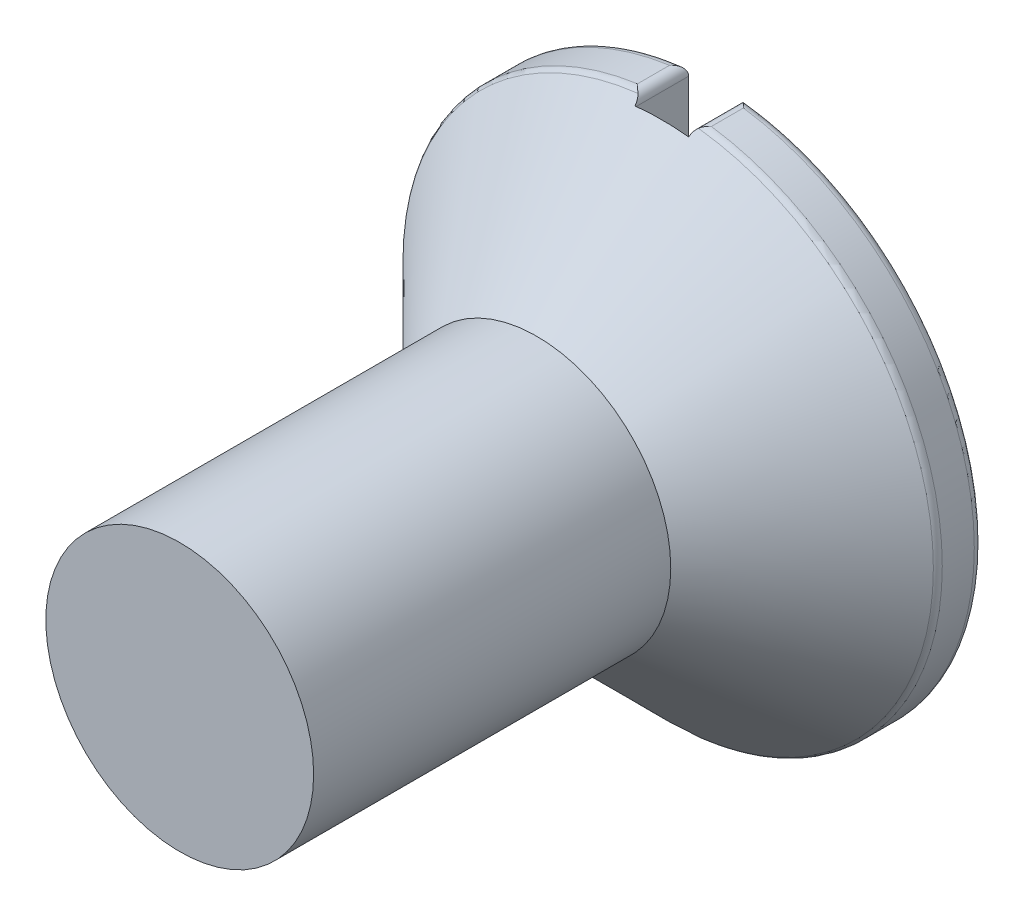
SolidWorks part; units mm, degrees
ref_plane "Front" through (0, 0, 0) normal (0, 0, 1) x (1, 0, 0)
ref_plane "Top" through (0, 0, 0) normal (0, 1, 0) x (1, 0, 0)
ref_plane "Right" through (0, 0, 0) normal (1, 0, 0) x (0, 0, -1)
sketch "Sketch1" plane through (0, 0, 0) normal (0, 0, 1) x (1, 0, 0)
  circle A0 centre (0, 0) radius 3
  dimension "D1" = 6
extrude "Base-Extrude" add sketch "Sketch1" along normal blind 1.5 draft 45
sketch "Sketch2" plane through (0, 0, 1.5) normal (0, 0, 1) x (1, 0, 0)
  circle A0 centre (0, 0) radius 1.5
  dimension "D1" = 3
extrude "Boss-Extrude1" add sketch "Sketch2" along normal blind 4
sketch "Sketch5" plane through (0, 0, 0) normal (0, 0, -1) x (-1, 0, 0)
  circle A0 centre (0, 0) radius 3
extrude "Boss-Extrude2" add sketch "Sketch5" along normal blind 0.5
sketch "Sketch6" plane through (0, 0, -0.5) normal (0, 0, -1) x (-1, 0, 0)
  line L1 (-0.3, 2.985) -> (0.3, 2.985)
  line L2 (-0.3, 2.985) -> (-0.3, -2.985)
  line L3 (-0.3, -2.985) -> (0.3, -2.985)
  line L4 (0.3, 2.985) -> (0.3, -2.985)
  circle A0 centre (0, 0) radius 3 construction
  dimension "D1" = 0.3
  dimension "D2" = 0.6
extrude "Cut-Extrude2" cut sketch "Sketch6" against normal blind 0.6
fillet "Fillet1" radius 0.1 12 edges at (3, 0, 0) (0.3, -2.985, -0.25) (-3, 0, 0) (-0.3, 2.985, -0.25) (3, 0, -0.5) (-3, 0, -0.5) (0.3, 2.985, -0.25) (-0.3, -2.985, -0.25)
